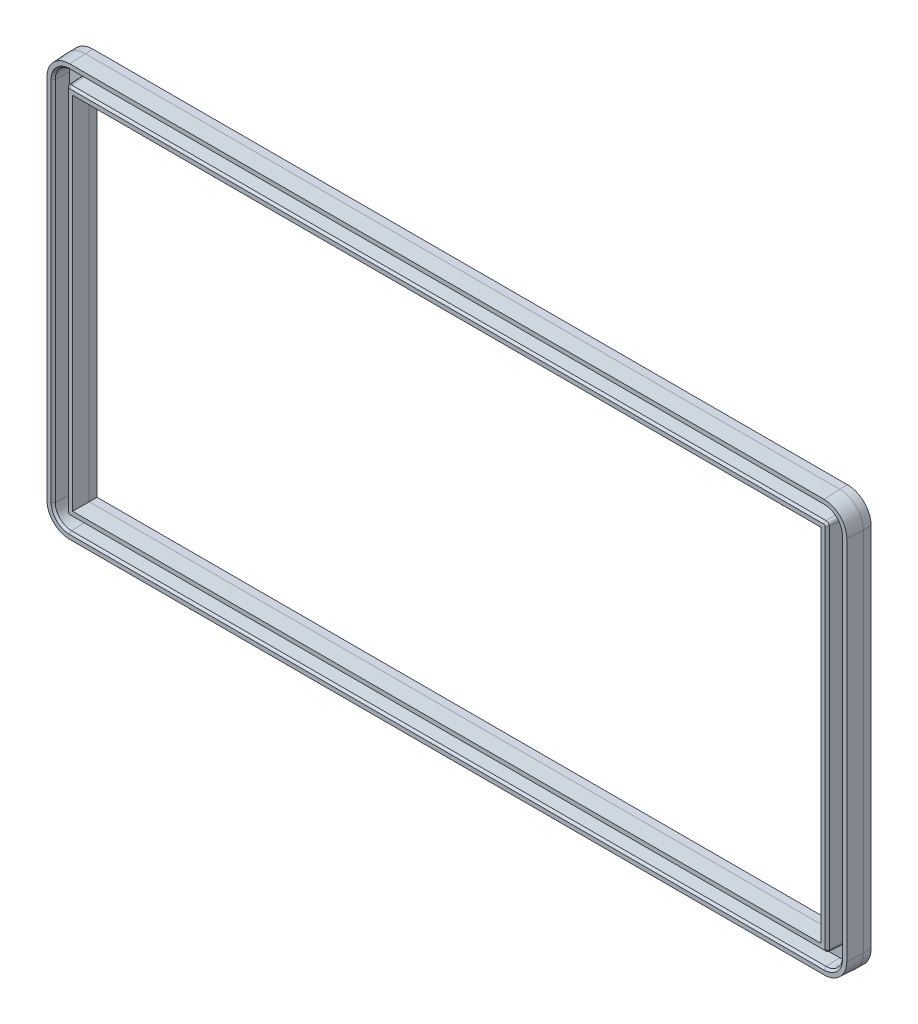
SolidWorks part; units mm, degrees
note: The reader was unsure of these and kept them because the rebuilt part matched: shared geometry of "Esquisse1<4>".
ref_plane "Plan de face" through (0, 0, 0) normal (0, 0, 1) x (1, 0, 0)
ref_plane "Plan de dessus" through (0, 0, 0) normal (0, 1, 0) x (1, 0, 0)
ref_plane "Plan de droite" through (0, 0, 0) normal (1, 0, 0) x (0, 0, -1)
sketch "Esquisse1" plane through (0, 0, 0) normal (0, 0, 1) x (1, 0, 0)
  line L0 (95.25, 0) -> (95.25, -91.5) construction
  line L1 (0, 0) -> (190.5, 0)
  line L2 (0, 0) -> (0, -91.5)
  line L3 (0, -91.5) -> (190.5, -91.5)
  line L4 (190.5, 0) -> (190.5, -91.5)
  line L5 (95.25, 0) -> (95.25, -91.5) construction
  line L6 (-1, -98.5) -> (191.5, -98.5)
  line L7 (-7, -92.5) -> (-7, 1)
  line L8 (-1, 7) -> (191.5, 7)
  line L9 (197.5, -92.5) -> (197.5, 1)
  line L10 (-7, -98.5) -> (197.5, 7) construction
  line L11 (-7, 7) -> (197.5, -98.5) construction
  line L16 (0, -45.75) -> (8.218, -45.75) construction
  line L17 (190.5, -45.75) -> (182.282, -45.75) construction
  line L19 (-1, -93.5) -> (191.5, -93.5)
  line L20 (-2, -92.5) -> (-2, 1)
  line L21 (-1, 2) -> (191.5, 2)
  line L22 (192.5, -92.5) -> (192.5, 1)
  line L23 (-2, -93.5) -> (192.5, 2) construction
  line L24 (-2, 2) -> (192.5, -93.5) construction
  line L25 (-1, -96.5) -> (191.5, -96.5)
  line L26 (-5, -92.5) -> (-5, 1)
  line L27 (-1, 5) -> (191.5, 5)
  line L28 (195.5, -92.5) -> (195.5, 1)
  line L29 (-5, -96.5) -> (195.5, 5) construction
  line L30 (-5, 5) -> (195.5, -96.5) construction
  arc A2 (-5, 1) -> (-1, 5) centre (-1, 1) cw
  arc A3 (-5, -92.5) -> (-1, -96.5) centre (-1, -92.5) ccw
  arc A4 (191.5, -96.5) -> (195.5, -92.5) centre (191.5, -92.5) ccw
  arc A5 (195.5, 1) -> (191.5, 5) centre (191.5, 1) ccw
  arc A6 (-1, -93.5) -> (-2, -92.5) centre (-1, -92.5) cw
  arc A7 (191.5, -93.5) -> (192.5, -92.5) centre (191.5, -92.5) ccw
  arc A8 (192.5, 1) -> (191.5, 2) centre (191.5, 1) ccw
  arc A9 (-1, 2) -> (-2, 1) centre (-1, 1) ccw
  arc A10 (-1, 7) -> (-7, 1) centre (-1, 1) ccw
  arc A11 (-1, -98.5) -> (-7, -92.5) centre (-1, -92.5) cw
  arc A12 (191.5, 7) -> (197.5, 1) centre (191.5, 1) cw
  arc A13 (197.5, -92.5) -> (191.5, -98.5) centre (191.5, -92.5) cw
  point P7 (95.25, -45.75)
  point P13 (95.25, -45.75)
  point P16 (95.25, -45.75)
  point P40 (95.25, -45.75)
  dimension "D2" = 200.5
  dimension "D9" = 194.5
  dimension "D12" = 4
  dimension "D13" = 1
  dimension "D14" = 6
  dimension "D1" = 190.5
  dimension "104" = 91.5
  dimension "D3" = 3
  dimension "D4" = 3
  dimension "D5" = 2
  dimension "D6" = 2
  dimension "D7" = 2
  dimension "D8" = 2
  dimension "D10" = 95.5
  dimension "D11" = 101.5
extrude "Boss.-Extru.1" add sketch "Esquisse1" along normal blind 4 draft 3 contours L19 L22 L21 L20 L1 L4 L3 L2 | L6 L9 L8 L7 L28 L25 L26 L27
extrude "Boss.-Extru.2" add sketch "Esquisse1<4>" against normal blind 2 contours L6 L9 L8 L7 L28 L25 L26 L27 | L25 L28 L27 L26 L22 L19 L20 L21 | L19 L22 L21 L20 L1 L4 L3 L2
sketch "Esquisse1<4>" plane through (0, 0, 0) normal (0, 0, 1) x (1, 0, 0) same geometry as "Esquisse1"
chamfer "Chanfrein1" distance 0.5 angle 45 8 edges at (95.25, 1.7904, 4) (192.2904, -45.75, 4) (95.25, -93.2904, 4) (-1.7904, -45.75, 4) (-1.5589, -93.0589, 4) (192.0589, -93.0589, 4) (-1.5589, 1.5589, 4) (192.0589, 1.5589, 4)
chamfer "Chanfrein2" distance 0.5 angle 45 8 edges at (-5.2096, -45.75, 4) (95.25, -96.7096, 4) (195.7096, -45.75, 4) (95.25, 5.2096, 4) (-3.9767, 3.9767, 4) (194.4767, 3.9767, 4) (-3.9767, -95.4767, 4) (194.4767, -95.4767, 4)
